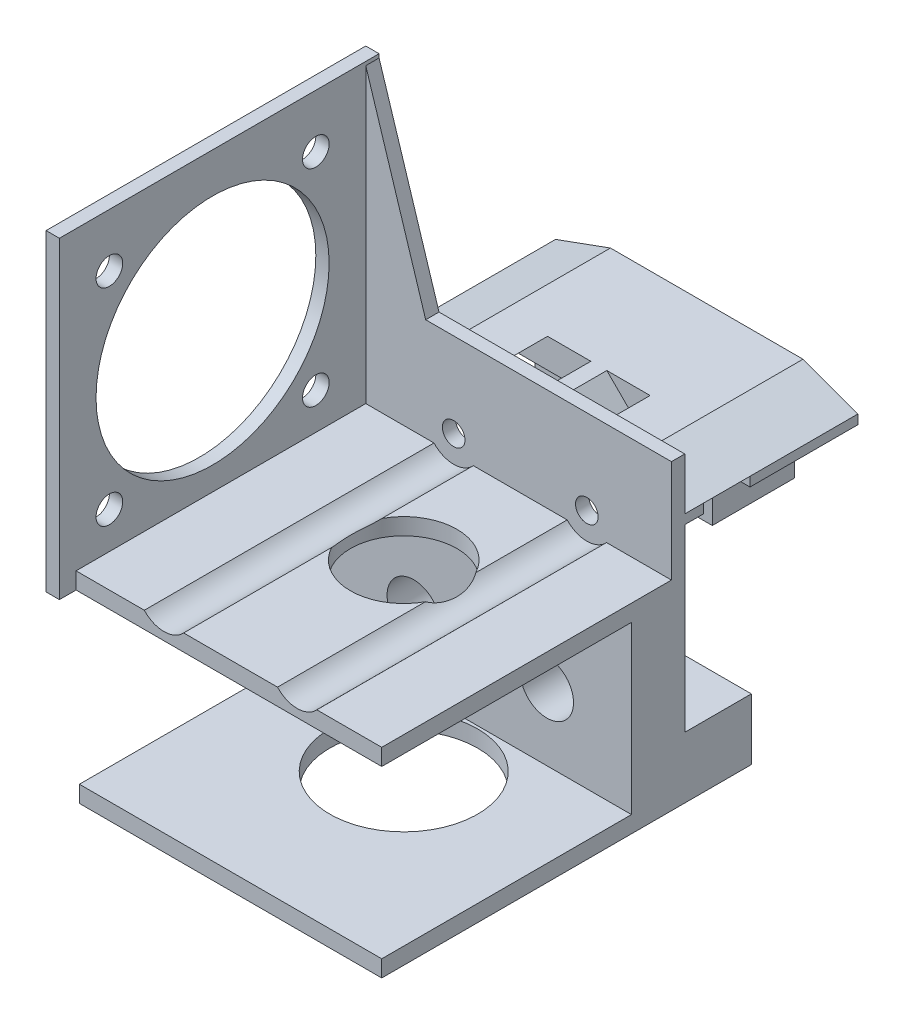
SolidWorks part; units mm, degrees
ref_plane "Front Plane" through (0, 0, 0) normal (0, 0, 1) x (1, 0, 0)
ref_plane "Top Plane" through (0, 0, 0) normal (0, 1, 0) x (1, 0, 0)
ref_plane "Right Plane" through (0, 0, 0) normal (1, 0, 0) x (0, 0, -1)
sketch "Sketch1" plane through (0, 0, 0) normal (0, 0, 1) x (1, 0, 0)
  line L1 (0, 0) -> (45.4, 0)
  line L2 (0, 0) -> (0, 45.4)
  line L3 (0, 45.4) -> (45.4, 45.4)
  line L4 (45.4, 0) -> (45.4, 45.4)
  dimension "D1" = 45.4
  dimension "D2" = 45.4
extrude "Boss-Extrude1" add sketch "Sketch1" along normal blind 12
sketch "Sketch2" plane through (0, 0, 0) normal (0, 0, -1) x (-1, 0, 0)
  line L0 (-45.4, 0) -> (-45.4, 45.4) construction
  line L1 (-45.4, 36.2) -> (0, 36.2)
  line L2 (-45.4, 36.2) -> (-45.4, 9.2)
  line L3 (-45.4, 9.2) -> (0, 9.2)
  line L4 (0, 36.2) -> (0, 9.2)
  line L5 (0, 45.4) -> (0, 0) construction
  line L6 (-45.4, 22.7) -> (0, 22.7) construction
  point P13 (-45.4, 22.7)
  dimension "D1" = 27
extrude "Cut-Extrude1" cut sketch "Sketch2" against normal blind 10
sketch "Sketch13" plane through (0, 0, 12) normal (0, 0, 1) x (1, 0, 0)
  line L0 (22.7, 45.4) -> (22.7, 0) construction
  line L1 (32.7, 12.7) -> (12.7, 12.7) construction
  line L2 (32.7, 12.7) -> (32.7, 32.7) construction
  line L3 (32.7, 32.7) -> (12.7, 32.7) construction
  line L4 (12.7, 12.7) -> (12.7, 32.7) construction
  line L5 (32.7, 12.7) -> (12.7, 32.7) construction
  line L6 (32.7, 32.7) -> (12.7, 12.7) construction
  line L7 (45.4, 45.4) -> (0, 45.4) construction
  line L8 (0, 0) -> (45.4, 0) construction
  line L9 (0, 22.7) -> (45.4, 22.7) construction
  line L10 (0, 9.2) -> (0, 36.2) construction
  line L11 (45.4, 36.2) -> (45.4, 9.2) construction
  circle A4 centre (32.7, 32.7) radius 1.7
  circle A5 centre (12.7, 32.7) radius 1.7
  circle A6 centre (32.7, 12.7) radius 1.7
  circle A7 centre (12.7, 12.7) radius 1.7
  point P12 (22.7, 22.7)
  point P31 (22.7, 22.7)
  dimension "D1" = 3.4
  dimension "D2" = 20
  dimension "D3" = 20
extrude "Cut-Extrude4" cut sketch "Sketch13" against normal up to next
sketch "Sketch20" plane through (45.4, 0, 0) normal (1, 0, 0) x (0, 0, -1)
  line L1 (-7.2, 36.2) -> (-0.2, 36.2)
  line L2 (-7.2, 36.2) -> (-7.2, 37.6)
  line L3 (-7.2, 37.6) -> (-0.2, 37.6)
  line L4 (-0.2, 36.2) -> (-0.2, 37.6)
  line L5 (-10, 36.2) -> (0, 36.2) construction
  line L6 (0, 36.2) -> (0, 45.4) construction
  dimension "D1" = 1.4
  dimension "D2" = 0.2
  dimension "D3" = 7
extrude "Cut-Extrude10" cut sketch "Sketch20" against normal blind 15
sketch "Sketch21" plane through (45.4, 0, 0) normal (1, 0, 0) x (0, 0, -1)
  line L0 (-0.2, 37.6) -> (-7.2, 37.6) construction
  line L1 (0, 45.4) -> (-10, 45.4)
  line L2 (0, 45.4) -> (0, 40.6)
  line L3 (0, 40.6) -> (-10, 40.6)
  line L4 (-10, 45.4) -> (-10, 40.6)
  dimension "D1" = 10
  dimension "D2" = 3
extrude "Cut-Extrude11" cut sketch "Sketch21" against normal through all
sketch "Sketch22" plane through (0, 0, 0) normal (-1, 0, 0) x (0, 0, 1)
  line L0 (10, 36.2) -> (0, 36.2) construction
  line L1 (0.2, 36.2) -> (7.2, 36.2)
  line L2 (0.2, 36.2) -> (0.2, 37.6)
  line L3 (0.2, 37.6) -> (7.2, 37.6)
  line L4 (7.2, 36.2) -> (7.2, 37.6)
  line L5 (0, 40.6) -> (0, 36.2) construction
  dimension "D1" = 7
  dimension "D2" = 0.2
  dimension "D3" = 1.4
extrude "Cut-Extrude12" cut sketch "Sketch22" against normal blind 15
sketch "Sketch29" plane through (0, 0, 12) normal (0, 0, 1) x (1, 0, 0)
  line L0 (0, 0) -> (45.4, 0) construction
  line L1 (0, 0) -> (45.4, 0)
  line L2 (0, 0) -> (0, 30)
  line L3 (0, 30) -> (45.4, 30)
  line L4 (45.4, 0) -> (45.4, 30)
  line L5 (0, 45.4) -> (0, 0) construction
  line L7 (22.7, 45.4) -> (22.7, 0) construction
  line L8 (45.4, 45.4) -> (0, 45.4) construction
  dimension "D3" = 30
extrude "Boss-Extrude6" add sketch "Sketch29" along normal blind 43.5
sketch "Sketch26" plane through (0, 0, 0) normal (0, 0, -1) x (-1, 0, 0)
  line L1 (-45.4, 40.6) -> (0, 40.6)
  line L2 (-45.4, 40.6) -> (-45.4, 36.2)
  line L3 (-45.4, 36.2) -> (0, 36.2)
  line L4 (0, 40.6) -> (0, 36.2)
  line L5 (0, 36.2) -> (-45.4, 36.2) construction
  line L6 (-45.4, 36.2) -> (-45.4, 40.6) construction
  line L7 (0, 40.6) -> (0, 36.2) construction
  line L8 (0, 40.6) -> (-45.4, 40.6) construction
extrude "Boss-Extrude4" add sketch "Sketch26" along normal blind 16
sketch "Sketch23" plane through (0, 40.6, 0) normal (0, 1, 0) x (1, 0, 0)
  line L1 (30.4, -0.2) -> (28.4, -0.2)
  line L2 (30.4, -0.2) -> (30.4, -7.2)
  line L3 (30.4, -7.2) -> (28.4, -7.2)
  line L4 (28.4, -0.2) -> (28.4, -7.2)
  line L5 (17, -7.2) -> (15, -7.2)
  line L6 (17, -7.2) -> (17, -0.2)
  line L7 (17, -0.2) -> (15, -0.2)
  line L8 (15, -7.2) -> (15, -0.2)
  line L9 (45.4, -10) -> (45.4, 16) construction
  line L10 (0, -10) -> (0, 16) construction
  line L13 (0, -10) -> (45.4, -10) construction
  dimension "D1" = 2
  dimension "D2" = 2
  dimension "D3" = 7
  dimension "D4" = 7
  dimension "D5" = 2.8
  dimension "D7" = 15
  dimension "D8" = 15
extrude "Cut-Extrude13" cut sketch "Sketch23" along normal blind 15 and the other way blind 15
sketch "Sketch17" plane through (0, 0, 12) normal (0, 0, 1) x (1, 0, 0)
  line L1 (12.7, 12.7) -> (32.7, 12.7) construction
  line L2 (12.7, 12.7) -> (12.7, 32.7) construction
  line L3 (12.7, 32.7) -> (32.7, 32.7) construction
  line L4 (32.7, 12.7) -> (32.7, 32.7) construction
  line L5 (12.7, 12.7) -> (32.7, 32.7) construction
  line L6 (12.7, 32.7) -> (32.7, 12.7) construction
  line L9 (22.7, 45.4) -> (22.7, 0) construction
  line L10 (45.4, 45.4) -> (0, 45.4) construction
  circle A0 centre (12.7, 32.7) radius 4
  circle A4 centre (32.7, 32.7) radius 4
  circle A5 centre (32.7, 12.7) radius 4
  circle A6 centre (12.7, 12.7) radius 4
  point P12 (22.7, 22.7)
  dimension "D1" = 8
  dimension "D2" = 20
  dimension "D3" = 20
extrude "Cut-Extrude8" cut sketch "Sketch17" along normal through all
chamfer "Chamfer1" distance 3 angle 70 1 edges at (45.4, 40.6, -3) first distance on face at (45.4, 29.4, 9.8625)
chamfer "Chamfer2" distance 3 angle 70 1 edges at (0, 40.6, -3) first distance on face at (0, 29.4, 9.8625)
sketch "Sketch24" plane through (0, 0, 0) normal (0, 0, -1) x (-1, 0, 0)
  line L0 (0, 0) -> (-45.4, 0) construction
  line L1 (-12, 0) -> (-10, 0)
  line L2 (-12, 0) -> (-12, 9.2)
  line L3 (-12, 9.2) -> (-10, 9.2)
  line L4 (-10, 0) -> (-10, 9.2)
  line L5 (-45.4, 9.2) -> (0, 9.2) construction
  line L6 (0, 9.2) -> (0, 0) construction
  dimension "D1" = 2
  dimension "D2" = 10
extrude "Boss-Extrude2" add sketch "Sketch24" along normal blind 10.25
sketch "Sketch25" plane through (10, 0, 0) normal (-1, 0, 0) x (0, 0, 1)
  line L0 (-10.25, 0) -> (0, 0) construction
  line L1 (-10.25, 9.2) -> (-8.75, 9.2)
  line L2 (-10.25, 9.2) -> (-10.25, 0)
  line L3 (-10.25, 0) -> (-8.75, 0)
  line L4 (-8.75, 9.2) -> (-8.75, 0)
  dimension "D1" = 1.5
extrude "Boss-Extrude3" add sketch "Sketch25" along normal blind 10
fillet "Fillet1" radius 4 2 edges at (12, 4.6, -10.25) (10, 4.6, -8.75)
chamfer "Chamfer3" distance 3 angle 45 2 edges at (15, 37.6, 3.7) (30.4, 37.6, 3.7)
chamfer "Chamfer4" distance 4.5 angle 45 2 edges at (28.4, 40.6, 3.7) (17, 40.6, 3.7)
sketch "Sketch27" plane through (0, 36.2, 0) normal (0, -1, 0) x (1, 0, 0)
  line L0 (45.4, -16) -> (0, -16) construction
  line L1 (35.878, -16) -> (9.2478, -16)
  line L2 (35.878, -16) -> (35.878, -3.6551)
  line L3 (35.878, -3.6551) -> (9.2478, -3.6551)
  line L4 (9.2478, -16) -> (9.2478, -3.6551)
extrude "Boss-Extrude5" add sketch "Sketch27" along normal blind 11.7
sketch "Sketch36" plane through (45.4, 0, 0) normal (1, 0, 0) x (0, 0, -1)
  line L0 (-55.5, 30) -> (-12, 30) construction
  line L1 (-55.5, 27.5) -> (-18, 27.5)
  line L2 (-55.5, 27.5) -> (-55.5, 2.5)
  line L3 (-55.5, 2.5) -> (-18, 2.5)
  line L4 (-18, 27.5) -> (-18, 2.5)
  line L5 (-10, 36.2) -> (-10, 9.2) construction
  line L6 (-55.5, 0) -> (0, 0) construction
  line L7 (-55.5, 0) -> (-55.5, 30) construction
  dimension "D1" = 2.5
  dimension "D2" = 8
  dimension "D3" = 2.5
extrude "Cut-Extrude18" cut sketch "Sketch36" against normal through all
sketch "Sketch28" plane through (0, 24.5, 0) normal (0, -1, 0) x (1, 0, 0)
  circle A0 centre (31.698, -9.7656) radius 1.5
  circle A1 centre (13.6999, -9.7639) radius 1.5
  dimension "D1" = 3
  dimension "D2" = 3
extrude "Cut-Extrude14" cut sketch "Sketch28" against normal blind 10
sketch "Sketch31" plane through (0, 30, 0) normal (0, 1, 0) x (1, 0, 0)
  line L0 (29.7487, -12) -> (15.6513, -12) construction
  line L1 (22.7, -29.5) -> (22.7, -12) construction
  line L3 (45.4, -12) -> (0, -12) construction
  circle A0 centre (22.7, -29.5) radius 8
  point P5 (0, 0)
  dimension "D1" = 16
  dimension "D2" = 17.5
extrude "Cut-Extrude15" cut sketch "Sketch31" against normal blind 35
sketch "Sketch32" plane through (0, 0, 0) normal (0, -1, 0) x (1, 0, 0)
  circle A1 centre (22.7, 29.5) radius 11.1
  dimension "D1" = 22.2
extrude "Cut-Extrude16" cut sketch "Sketch32" against normal up to surface (27.5 mm away) up to face at (14.7, 27.5, 29.5)
sketch "Sketch33" plane through (0, 0, 0) normal (-1, 0, 0) x (0, 0, 1)
  line L1 (10, 45.4) -> (12, 45.4)
  line L2 (10, 45.4) -> (10, 27.5)
  line L4 (12, 45.4) -> (12, 30)
  line L5 (12, 30) -> (55.5, 30)
  line L6 (55.5, 30) -> (55.5, 27.5)
  line L8 (55.5, 27.5) -> (10, 27.5)
  dimension "D1" = 2.5
extrude "Boss-Extrude7" add sketch "Sketch33" along normal blind 0.5
sketch "Sketch34" plane through (-0.5, 0, 0) normal (-1, 0, 0) x (0, 0, 1)
  line L0 (10, 27.5) -> (55.5, 27.5) construction
  line L1 (10, 27.5) -> (58, 27.5)
  line L2 (10, 27.5) -> (10, 74.5)
  line L3 (10, 74.5) -> (58, 74.5)
  line L4 (58, 27.5) -> (58, 74.5)
  line L6 (10, 45.4) -> (10, 27.5) construction
  dimension "D1" = 48
  dimension "D2" = 47
extrude "Boss-Extrude8" add sketch "Sketch34" along normal blind 2
sketch "Sketch35" plane through (-2.5, 0, 0) normal (-1, 0, 0) x (0, 0, 1)
  line L0 (10, 74.5) -> (10, 27.5) construction
  line L1 (19.5, 66.5) -> (50.5, 66.5) construction
  line L2 (19.5, 66.5) -> (19.5, 35.5) construction
  line L3 (19.5, 35.5) -> (50.5, 35.5) construction
  line L4 (50.5, 66.5) -> (50.5, 35.5) construction
  line L5 (10, 27.5) -> (58, 27.5) construction
  line L6 (35, 66.5) -> (35, 35.5) construction
  line L7 (19.5, 51) -> (50.5, 51) construction
  circle A0 centre (19.5, 66.5) radius 2
  circle A1 centre (50.5, 66.5) radius 2
  circle A2 centre (50.5, 35.5) radius 2
  circle A3 centre (19.5, 35.5) radius 2
  circle A4 centre (35, 51) radius 17.5
  point P19 (35, 51)
  dimension "D1" = 35
  dimension "D2" = 4
  dimension "D3" = 31
  dimension "D4" = 9.5
  dimension "D5" = 8
extrude "Cut-Extrude17" cut sketch "Sketch35" against normal blind 10
chamfer "Chamfer7" distance 9 angle 72.5 1 edges at (-0.5, 45.4, 11) first distance on face at (22.45, 45.4, 11)
